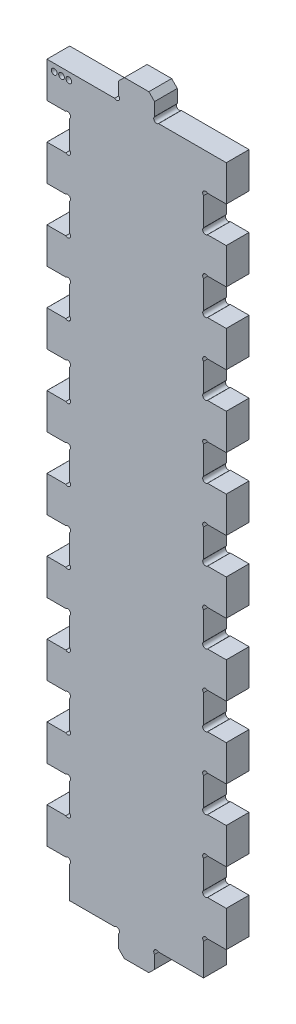
SolidWorks part; units mm, degrees
material "PVC Rigid"
ref_plane "Front Plane" through (0, 0, 0) normal (0, 0, 1) x (1, 0, 0)
ref_plane "Top Plane" through (0, 0, 0) normal (0, 1, 0) x (1, 0, 0)
ref_plane "Right Plane" through (0, 0, 0) normal (1, 0, 0) x (0, 0, -1)
sketch "Model" [suppressed]
  dimension "D3" = 0.7937
  dimension "D1" = 10
  dimension "D2" = 10
sketch "Sketch1" plane through (0, 0, 0) normal (0, 0, 1) x (1, 0, 0)
  line L1 (0, 0) -> (50, 0)
  line L2 (0, 0) -> (0, 200.0001)
  line L3 (0, 200.0001) -> (50, 200.0001)
  line L4 (50, 0) -> (50, 200.0001)
  dimension "D1" = 200.0001
  dimension "D2" = 50
extrude "Boss-Extrude1" add sketch "Sketch1" along normal blind 6.35
sketch "Sketch2" plane through (0, 0, 0) normal (0, 0, 1) x (1, 0, 0)
  line L0 (0, 100.0001) -> (50, 100.0001) construction
  line L1 (50, 200.0001) -> (0, 200.0001) construction
  line L2 (25, 200.0001) -> (25, 203.1751) construction
  line L3 (20, 206.3501) -> (30, 206.3501)
  line L4 (20, 206.3501) -> (20, 200.0001)
  line L5 (20, 200.0001) -> (30, 200.0001)
  line L6 (30, 206.3501) -> (30, 200.0001)
  line L7 (20, 206.3501) -> (30, 200.0001) construction
  line L8 (20, 200.0001) -> (30, 206.3501) construction
  line L9 (0, 200.0001) -> (0, 0) construction
  line L10 (50, 0) -> (50, 200.0001) construction
  line L11 (20, 0) -> (30, -6.35) construction
  line L12 (20, -6.35) -> (30, 0) construction
  line L13 (25, 0) -> (25, -3.175) construction
  line L14 (30, -6.35) -> (30, 0)
  line L15 (20, 0) -> (30, 0)
  line L16 (20, -6.35) -> (20, 0)
  line L17 (20, -6.35) -> (30, -6.35)
  dimension "D1" = 6.35
  dimension "D2" = 10
extrude "Boss-Extrude2" add sketch "Sketch2" along normal blind 6.35
sketch "Sketch3" plane through (0, 0, 6.35) normal (0, 0, 1) x (1, 0, 0)
  line L0 (25, 206.3501) -> (25, -6.35) construction
  line L1 (30, 206.3501) -> (20, 206.3501) construction
  line L2 (20, -6.35) -> (30, -6.35) construction
  line L3 (6.35, 200.0001) -> (6.35, 0) construction
  line L4 (20, 200.0001) -> (0, 200.0001) construction
  line L5 (0, 0) -> (20, 0) construction
  line L6 (0, 200.0001) -> (0, 0) construction
  line L7 (6.35, 0) -> (0, 0)
  line L8 (6.35, 0) -> (6.35, 10)
  line L9 (6.35, 10) -> (0, 10)
  line L10 (0, 0) -> (0, 10)
  line L11 (50, 0) -> (50, 10)
  line L12 (43.65, 10) -> (50, 10)
  line L13 (43.65, 0) -> (43.65, 10)
  line L14 (43.65, 0) -> (50, 0)
  dimension "D1" = 6.35
  dimension "D2" = 10
extrude "Cut-Extrude1" cut sketch "Sketch3" against normal blind 6.35
pattern_linear "LPattern2" count 10 spacing 20 along (0, 1, 0) of "Cut-Extrude1"
sketch "Sketch4" plane through (0, 0, 6.35) normal (0, 0, 1) x (1, 0, 0)
  line L0 (0, 10) -> (6.35, 0) construction
  line L1 (6.35, 10) -> (5.2275, 10) construction
  line L2 (0.5613, 0.5613) -> (5.7887, 0.5613) construction
  line L3 (0.5613, 0.5613) -> (0.5613, 9.4387) construction
  line L4 (0.5613, 9.4387) -> (5.7887, 9.4387) construction
  line L5 (5.7887, 0.5613) -> (5.7887, 9.4387) construction
  line L6 (0.5613, 0.5613) -> (5.7887, 9.4387) construction
  line L7 (0.5613, 9.4387) -> (5.7887, 0.5613) construction
  line L8 (6.35, 10) -> (0, 10) construction
  line L9 (6.35, 10) -> (6.35, 8.8775) construction
  line L10 (6.35, 0) -> (6.35, 10) construction
  line L11 (25, 206.3501) -> (25, -6.35) construction
  line L12 (30, 206.3501) -> (20, 206.3501) construction
  line L13 (20, -6.35) -> (30, -6.35) construction
  line L14 (44.2113, 9.4387) -> (44.2113, 20.5613) construction
  line L15 (43.65, 10) -> (43.65, 8.8775) construction
  line L16 (49.4387, 9.4387) -> (44.2113, 0.5613) construction
  line L17 (49.4387, 0.5613) -> (44.2113, 9.4387) construction
  line L18 (44.2113, 0.5613) -> (44.2113, 9.4387) construction
  line L19 (49.4387, 9.4387) -> (44.2113, 9.4387) construction
  line L20 (49.4387, 0.5613) -> (49.4387, 9.4387) construction
  line L21 (49.4387, 0.5613) -> (44.2113, 0.5613) construction
  line L22 (43.65, 10) -> (44.7725, 10) construction
  line L23 (5.7887, 9.4387) -> (5.7887, 20.5613) construction
  line L24 (50, 10) -> (43.65, 0) construction
  circle A0 centre (5.7887, 9.4387) radius 0.7938
  circle A4 centre (5.7887, 20.5613) radius 0.7938
  circle A7 centre (44.2113, 20.5613) radius 0.7937
  circle A8 centre (44.2113, 9.4387) radius 0.7937
  point P4 (3.175, 5)
  point P40 (46.825, 5)
  dimension "D1" = 1.5875
extrude "Cut-Extrude3" cut sketch "Sketch4" against normal blind 6.35
pattern_linear "LPattern3" count 9 spacing 20 along (0, 1, 0) of "Cut-Extrude3"
sketch "Sketch8" [suppressed] plane through (0, 0, 6.35) normal (0, 0, 1) x (1, 0, 0)
  line L0 (6.35, 200.0001) -> (6.35, 0) construction
  line L1 (20, 200.0001) -> (0, 200.0001) construction
  line L2 (0, 0) -> (20, 0) construction
  line L3 (0, 200.0001) -> (0, 0) construction
  line L4 (43.65, 200.0001) -> (43.65, 0) construction
  line L5 (0, 0) -> (6.35, 0)
  line L6 (0, 0) -> (0, 10)
  line L7 (0, 10) -> (6.35, 10)
  line L8 (6.35, 0) -> (6.35, 10)
  line L9 (50, 200.0001) -> (30, 200.0001) construction
  line L10 (30, 0) -> (50, 0) construction
  line L11 (50, 0) -> (50, 200.0001) construction
  line L12 (43.65, 10) -> (50, 10)
  line L13 (43.65, 10) -> (43.65, 20)
  line L14 (43.65, 20) -> (50, 20)
  line L15 (50, 10) -> (50, 20)
  dimension "D1" = 6.35
  dimension "D2" = 10
  dimension "D3" = 10
  dimension "D4" = 6.35
  dimension "D5" = 10
extrude "Cut-Extrude6" [suppressed] cut sketch "Sketch8" against normal through all
pattern_linear "LPattern4" [suppressed] count 10 spacing 20 of bodies 116
sketch "Sketch9" [suppressed] plane through (0, 0, 6.35) normal (0, 0, 1) x (1, 0, 0)
  line L0 (0, 30) -> (6.35, 20) construction
  line L1 (6.35, 30) -> (5.2275, 30) construction
  line L2 (0.5613, 20.5613) -> (5.7887, 20.5613) construction
  line L3 (0.5613, 20.5613) -> (0.5613, 29.4388) construction
  line L4 (0.5613, 29.4388) -> (5.7887, 29.4388) construction
  line L5 (5.7887, 20.5613) -> (5.7887, 29.4388) construction
  line L6 (0.5613, 20.5613) -> (5.7887, 29.4388) construction
  line L7 (0.5613, 29.4388) -> (5.7887, 20.5613) construction
  line L8 (6.35, 30) -> (0, 30) construction
  line L9 (6.35, 30) -> (6.35, 28.8775) construction
  line L10 (6.35, 20) -> (6.35, 30) construction
  line L11 (43.65, 20) -> (50, 10) construction
  line L12 (43.65, 20) -> (44.7725, 20) construction
  line L13 (44.2113, 10.5613) -> (49.4387, 10.5613) construction
  line L14 (44.2113, 10.5613) -> (44.2113, 19.4387) construction
  line L15 (44.2113, 19.4387) -> (49.4387, 19.4387) construction
  line L16 (49.4387, 10.5613) -> (49.4387, 19.4387) construction
  line L17 (44.2113, 10.5613) -> (49.4387, 19.4387) construction
  line L18 (44.2113, 19.4387) -> (49.4387, 10.5613) construction
  line L19 (50, 20) -> (43.65, 20) construction
  line L20 (43.65, 20) -> (43.65, 18.8775) construction
  line L21 (43.65, 20) -> (43.65, 10) construction
  line L22 (50, 20) -> (50, 30) construction
  circle A0 centre (5.7887, 29.4388) radius 0.7938
  circle A1 centre (5.7887, 20.5613) radius 0.7938
  circle A2 centre (44.2113, 19.4387) radius 0.7937
  circle A3 centre (44.2113, 10.5613) radius 0.7937
  point P4 (3.175, 25)
  point P23 (46.825, 15)
  dimension "D1" = 1.5875
  dimension "D2" = 10
extrude "Cut-Extrude7" [suppressed] cut sketch "Sketch9" against normal through all
pattern_linear "LPattern5" [suppressed] count 9 spacing 20 of bodies 118
sketch "Sketch10" [suppressed] plane through (0, 0, 6.35) normal (0, 0, 1) x (1, 0, 0)
  line L0 (0, 10) -> (6.35, 0) construction
  line L1 (5.2275, 10) -> (6.35, 10) construction
  line L2 (0.5613, 0.5613) -> (5.7887, 0.5613) construction
  line L3 (0.5613, 0.5613) -> (0.5613, 9.4387) construction
  line L4 (0.5613, 9.4387) -> (5.7887, 9.4387) construction
  line L5 (5.7887, 0.5613) -> (5.7887, 9.4387) construction
  line L6 (0.5613, 0.5613) -> (5.7887, 9.4387) construction
  line L7 (0.5613, 9.4387) -> (5.7887, 0.5613) construction
  line L8 (6.35, 10) -> (0, 10) construction
  line L9 (6.35, 10) -> (6.35, 8.8775) construction
  line L10 (6.35, 0) -> (6.35, 10) construction
  line L11 (6.35, 5) -> (3.175, 5) construction
  line L12 (0, 200.0001) -> (50, 0) construction
  line L13 (43.65, 200.0001) -> (50, 190.0001) construction
  line L14 (44.7725, 190.0001) -> (43.65, 190.0001) construction
  line L15 (44.2113, 190.5614) -> (49.4387, 190.5614) construction
  line L16 (44.2113, 190.5614) -> (44.2113, 199.4388) construction
  line L17 (44.2113, 199.4388) -> (49.4387, 199.4388) construction
  line L18 (49.4387, 190.5614) -> (49.4387, 199.4388) construction
  line L19 (44.2113, 190.5614) -> (49.4387, 199.4388) construction
  line L20 (44.2113, 199.4388) -> (49.4387, 190.5614) construction
  line L21 (43.65, 190.0001) -> (50, 190.0001) construction
  line L22 (43.65, 190.0001) -> (43.65, 191.1226) construction
  line L23 (43.65, 200.0001) -> (43.65, 190.0001) construction
  circle A0 centre (5.7887, 9.4387) radius 0.7938
  circle A2 centre (44.2113, 190.5614) radius 0.7937
  point P4 (3.175, 5)
  point P28 (46.825, 195.0001)
  dimension "D1" = 1.5875
  dimension "D2" = 1.5875
extrude "Cut-Extrude8" [suppressed] cut sketch "Sketch10" against normal through all
chamfer "Chamfer1" distance 1.5875 angle 45 4 edges at (30, -6.35, 3.175) (20, -6.35, 3.175) (20, 206.3501, 3.175) (30, 206.3501, 3.175)
sketch "Sketch5" plane through (0, 0, 6.35) normal (0, 0, 1) x (1, 0, 0)
  line L0 (6.35, 180.0001) -> (0, 190.0001) construction
  line L1 (6.35, 190.0001) -> (5.2275, 190.0001) construction
  line L2 (0.5613, 180.5614) -> (5.7887, 180.5614) construction
  line L3 (0.5613, 180.5614) -> (0.5613, 189.4388) construction
  line L4 (0.5613, 189.4388) -> (5.7887, 189.4388) construction
  line L5 (5.7887, 180.5614) -> (5.7887, 189.4388) construction
  line L6 (0.5613, 180.5614) -> (5.7887, 189.4388) construction
  line L7 (0.5613, 189.4388) -> (5.7887, 180.5614) construction
  line L8 (6.35, 190.0001) -> (0, 190.0001) construction
  line L9 (6.35, 190.0001) -> (6.35, 188.8776) construction
  line L10 (6.35, 181.1226) -> (6.35, 190.0001) construction
  line L15 (25, 206.3501) -> (25, -6.35) construction
  line L16 (28.4125, 206.3501) -> (21.5875, 206.3501) construction
  line L17 (21.5875, -6.35) -> (28.4125, -6.35) construction
  line L20 (43.65, 190.0001) -> (43.65, 188.8776) construction
  line L21 (49.4387, 189.4388) -> (44.2113, 180.5614) construction
  line L22 (49.4387, 180.5614) -> (44.2113, 189.4388) construction
  line L23 (44.2113, 180.5614) -> (44.2113, 189.4388) construction
  line L24 (49.4387, 189.4388) -> (44.2113, 189.4388) construction
  line L25 (49.4387, 180.5614) -> (49.4387, 189.4388) construction
  line L26 (49.4387, 180.5614) -> (44.2113, 180.5614) construction
  line L27 (43.65, 190.0001) -> (44.7725, 190.0001) construction
  line L28 (43.65, 180.0001) -> (50, 190.0001) construction
  line L29 (50, 100.0001) -> (0, 100.0001) construction
  arc A0 (5.2275, 180.0001) -> (6.35, 181.1226) centre (5.7887, 180.5614) ccw construction
  circle A1 centre (5.7887, 189.4388) radius 0.7938
  circle A4 centre (44.2113, 189.4388) radius 0.7937
  point P6 (3.175, 185.0001)
  point P51 (46.825, 185.0001)
  point P56 (25, 100.0001)
  dimension "D1" = 1.5875
extrude "Cut-Extrude4" cut sketch "Sketch5" against normal blind 6.35
sketch "Sketch11" plane through (0, 0, 0) normal (0, 0, 1) x (1, 0, 0)
  line L0 (28.4125, 206.3501) -> (21.5875, 206.3501) construction
  line L11 (20, 201.1226) -> (20, 200.0001) construction
  line L13 (20, 200.0001) -> (18.8775, 200.0001) construction
  line L15 (25, 206.3501) -> (25, -6.35) construction
  line L18 (30, 200.0001) -> (31.1225, 200.0001) construction
  line L19 (30, 201.1226) -> (30, 200.0001) construction
  line L29 (50, 100.0001) -> (0, 100.0001) construction
  circle A2 centre (19.4387, 200.5614) radius 0.7937
  circle A3 centre (30.5613, 200.5614) radius 0.7937
  circle A5 centre (19.4387, -0.5613) radius 0.7937
  circle A6 centre (30.5613, -0.5613) radius 0.7937
  point P56 (25, 100.0001)
  dimension "D1" = 1.5875
  dimension "D2" = 19.4387
  dimension "D3" = 100.0001
  dimension "D4" = 200.0001
extrude "Cut-Extrude10" cut sketch "Sketch11" along normal through all
sketch "Sketch6" plane through (0, 0, 6.35) normal (0, 0, 1) x (1, 0, 0)
  line L0 (6.604, 2.032) -> (43.65, 2.032) construction
  line L1 (43.65, 8.8775) -> (43.65, 0) construction
  line L2 (6.35, 0) -> (18.8775, 0) construction
  line L4 (0, 20) -> (0, 10) construction
  text T0 "CSR" font "Consolas" height 3.5
  dimension "D1" = 2.032
  dimension "D2" = 6.604
extrude "Cut-Extrude5" [suppressed] cut sketch "Sketch6" against normal blind 2.54
sketch "Sketch12" [suppressed] plane through (0, 0, 6.35) normal (0, 0, 1) x (1, 0, 0)
  line L0 (6.604, 2.032) -> (40.0372, 2.032) construction
  text T0 "COL_BIT" font "Consolas" height 3.5
  dimension "D1" = 2.032
  dimension "D2" = 6.604
extrude "Cut-Extrude11" [suppressed] cut sketch "Sketch12" against normal blind 2.54
sketch "Sketch13" plane through (0, 0, 6.35) normal (0, 0, 1) x (1, 0, 0)
  line L0 (0, 10) -> (6.35, 0) construction
  line L1 (5.2275, 10) -> (0, 10) construction
  line L2 (6.337, -0.0127) -> (0.013, -0.0127)
  line L3 (6.337, -0.0127) -> (6.337, 10.0127)
  line L4 (6.337, 10.0127) -> (0.013, 10.0127)
  line L5 (0.013, -0.0127) -> (0.013, 10.0127)
  line L6 (6.337, -0.0127) -> (0.013, 10.0127) construction
  line L7 (6.337, 10.0127) -> (0.013, -0.0127) construction
  line L8 (25, 206.3501) -> (25, -6.35) construction
  line L9 (28.4125, 206.3501) -> (21.5875, 206.3501) construction
  line L10 (21.5875, -6.35) -> (28.4125, -6.35) construction
  line L11 (43.663, 10.0127) -> (49.987, -0.0127) construction
  line L12 (43.663, -0.0127) -> (49.987, 10.0127) construction
  line L13 (50, 10) -> (43.65, 0) construction
  line L14 (49.987, -0.0127) -> (49.987, 10.0127)
  line L15 (43.663, 10.0127) -> (49.987, 10.0127)
  line L16 (43.663, -0.0127) -> (43.663, 10.0127)
  line L17 (43.663, -0.0127) -> (49.987, -0.0127)
  arc A0 (6.35, 8.8775) -> (5.2275, 10) centre (5.7887, 9.4387) ccw construction
  point P4 (3.175, 5)
  point P26 (46.825, 5)
  dimension "D1" = 0.0127
extrude "Cut-Extrude12" cut sketch "Sketch13" against normal through all
pattern_linear "LPattern6" count 10 spacing 20 along (0, 1, 0) of "Cut-Extrude12"
sketch "Sketch14" [suppressed] plane through (0, 0, 6.35) normal (0, 0, 1) x (1, 0, 0)
  line L0 (0, 10) -> (6.35, 0) construction
  line L1 (5.2275, 10) -> (0, 10) construction
  line L2 (0.013, -0.0127) -> (6.337, -0.0127)
  line L3 (0.013, -0.0127) -> (0.013, 10.0127)
  line L4 (0.013, 10.0127) -> (6.337, 10.0127)
  line L5 (6.337, -0.0127) -> (6.337, 10.0127)
  line L6 (0.013, -0.0127) -> (6.337, 10.0127) construction
  line L7 (0.013, 10.0127) -> (6.337, -0.0127) construction
  line L8 (43.65, 20) -> (50, 10) construction
  line L9 (50, 20) -> (44.7725, 20) construction
  line L10 (43.663, 9.9873) -> (49.987, 9.9873)
  line L11 (43.663, 9.9873) -> (43.663, 20.0127)
  line L12 (43.663, 20.0127) -> (49.987, 20.0127)
  line L13 (49.987, 9.9873) -> (49.987, 20.0127)
  line L14 (43.663, 9.9873) -> (49.987, 20.0127) construction
  line L15 (43.663, 20.0127) -> (49.987, 9.9873) construction
  arc A0 (6.35, 8.8775) -> (5.2275, 10) centre (5.7887, 9.4387) ccw construction
  arc A1 (44.7725, 20) -> (43.65, 18.8775) centre (44.2113, 19.4387) ccw construction
  point P4 (3.175, 5)
  point P9 (46.825, 15)
  dimension "D1" = 0.0127
  dimension "D2" = 0.0127
extrude "Cut-Extrude13" [suppressed] cut sketch "Sketch14" against normal through all
pattern_linear "LPattern7" [suppressed] count 10 spacing 20 of bodies 125
sketch "Sketch15" plane through (0, 0, 6.35) normal (0, 0, 1) x (1, 0, 0)
  line L1 (0, 200.0001) -> (2.032, 200.0001) construction
  line L2 (0, 200.0001) -> (0, 197.9681) construction
  line L3 (0, 197.9681) -> (2.032, 197.9681) construction
  line L4 (2.032, 200.0001) -> (2.032, 197.9681) construction
  circle A0 centre (2.032, 197.9681) radius 0.7938
  dimension "D2" = 1.5875
  dimension "D1" = 2.032
extrude "Cut-Extrude14" cut sketch "Sketch15" against normal blind 3.175
pattern_linear "LPattern8" count 3 spacing 2.032 along (1, 0, 0) of "Cut-Extrude14"
equation "\"tHeight\"=0.25"
equation "\"D1@Sketch2\"=\"tHeight\""
equation "\"tWidth\"=0.393701"
equation "\"D2@Sketch2\"=\"tWidth\""
equation "\"D1@Sketch1\"=\"tWidth\"*20"
equation "\"D1@Sketch3\"=\"tHeight\""
equation "\"D2@Sketch3\"=\"tWidth\""
equation "\"D3@LPattern2\"=\"tWidth\"*2"
equation "\"D3@LPattern3\"=\"tWidth\"*2"
equation "\"D1@Sketch8\"=\"tHeight\""
equation "\"D2@Sketch8\"=\"tWidth\""
equation "\"D3@Sketch8\"=\"tWidth\""
equation "\"D4@Sketch8\"=\"tHeight\""
equation "\"D5@Sketch8\"=\"tWidth\""
equation "\"D3@LPattern4\"=\"tWidth\"*2"
equation "\"D3@LPattern5\"=\"tWidth\"*2"
equation "\"D2@Sketch9\"=\"tWidth\""
equation "\"tol\"=0.0005"
equation "\"D1@Sketch13\"=\"tol\""
equation "\"D3@LPattern6\"=\"tWidth\"*2"
equation "\"D1@Sketch14\"=\"tol\""
equation "\"D2@Sketch14\"=\"tol\""
equation "\"version\"= 3"
equation "\"D1@LPattern8\"=\"version\""
